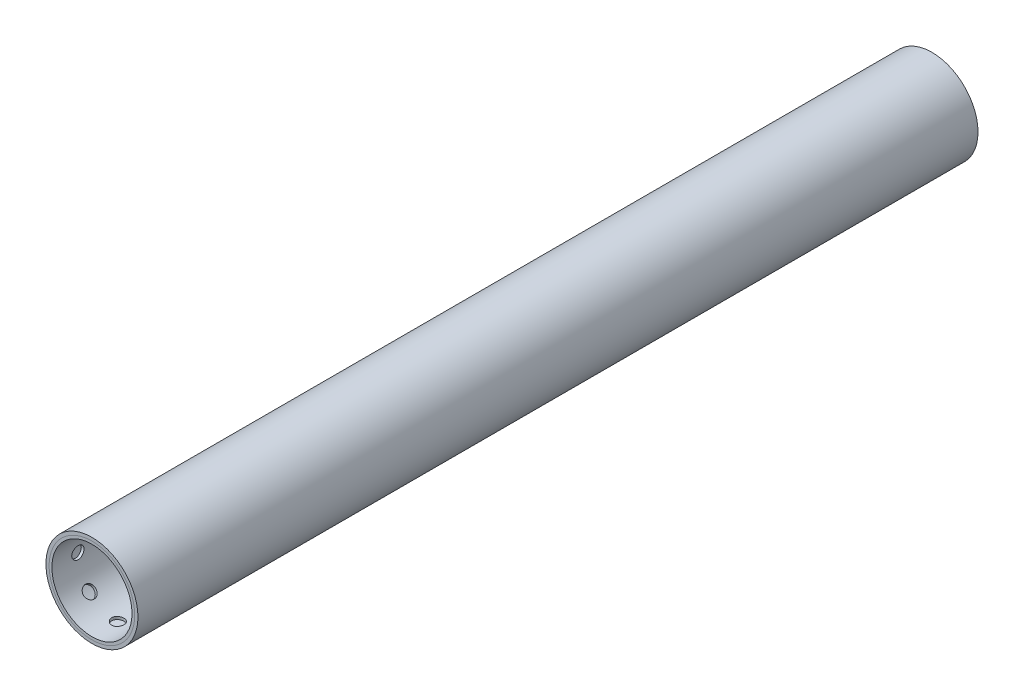
SolidWorks part; units mm, degrees
material "ASTM A53 Grade B"
ref_plane "Front Plane" through (0, 0, 0) normal (0, 0, 1) x (1, 0, 0)
ref_plane "Top Plane" through (0, 0, 0) normal (0, 1, 0) x (1, 0, 0)
ref_plane "Right Plane" through (0, 0, 0) normal (1, 0, 0) x (0, 0, -1)
sketch "Croquis1" plane through (0, 0, 0) normal (0, 0, 1) x (1, 0, 0)
  circle A0 centre (0, 0) radius 26.2509
  circle A1 centre (0, 0) radius 28.0509
  dimension "D1" = 52.5018
  dimension "D2" = 56.1018
extrude "Saliente-Extruir1" add sketch "Croquis1" against normal blind 550.5
sketch "Croquis2" plane through (0, 0, 0) normal (0, 0, 1) x (1, 0, 0)
  circle A0 centre (0, 0) radius 30.1625
  circle A3 centre (0, 0) radius 28.0509 construction
  circle A4 centre (0, 0) radius 28.0509
  dimension "D1" = 60.325
sketch "Croquis3" plane through (0, 0, 0) normal (1, 0, 0) x (0, 0, -1)
  line L0 (550.5, 28.0509) -> (535, 28.0509) construction
  point P4 (535, 28.0509)
  dimension "D1" = 15.5
sketch "Croquis14" plane through (0, 0, 0) normal (1, 0, 0) x (0, 0, -1)
  line L0 (550.5, 28.0509) -> (0, 28.0509) construction
  point P0 (17, 28.0509)
  dimension "D1" = 17
hole_wizard "Ø8.0mm Dowel Hole1" positions "Croquis3D7" profile "Croquis13" hole size "Ø8.0" standard "ANSI Metric"
sketch3d "Croquis3D7"
  point P0 (0, 28.0509, -535)
  point P4 (0, 0, 0)
  point P7 (0, 0, 0)
sketch "Croquis13" plane through (0, 28.0509, -535) normal (1, 0, 0) x (0, 0, 1)
  line L0 (0, 0) -> (0, 9.4034)
  line L1 (0, 9.4034) -> (4, 7)
  line L2 (4, 7) -> (4, 0)
  line L5 (4, 0) -> (0, 0)
  line L10 (0, 9.4034) -> (-4, 7) construction
  line L11 (0, -6.35) -> (0, 107.95) construction
  dimension "Hole Dia." = 8
  dimension "Hole Depth" = 7
  dimension "Drill Angle" = 118
hole_wizard "Ø8.0mm Dowel Hole2" positions "Croquis3D10" profile "Croquis17" hole size "Ø8.0" standard "ANSI Metric"
sketch3d "Croquis3D10"
  point P0 (0, 28.0509, -17)
  point P2 (0, 0, 0)
sketch "Croquis17" plane through (0, 28.0509, -17) normal (1, 0, 0) x (0, 0, 1)
  line L0 (0, 0) -> (0, 9.4034)
  line L1 (0, 9.4034) -> (4, 7)
  line L2 (4, 7) -> (4, 0)
  line L5 (4, 0) -> (0, 0)
  line L10 (0, 9.4034) -> (-4, 7) construction
  line L11 (0, -6.35) -> (0, 107.95) construction
  dimension "Hole Dia." = 8
  dimension "Hole Depth" = 7
  dimension "Drill Angle" = 118
pattern_circular "MatrizC1" count 8 over 360 about axis through (0, 0, -550.5) along (0, 0, 1) of "Ø8.0mm Dowel Hole1", "Ø8.0mm Dowel Hole2"
extrude "Saliente-Extruir2" add sketch "Croquis2" against normal blind 550.5 separate body
equation "\"IDcase\"= 52.5018"
equation "\"D1@Croquis1\"=\"IDcase\""
equation "\"ODcase\"= \"IDcase\" + 2 * \"CaseThickness\""
equation "\"D2@Croquis1\"=\"ODcase\""
equation "\"CaseLength\"= 525mm + 25 + 0.5"
equation "\"D1@Saliente-Extruir1\"=\"CaseLength\""
equation "\"CaseThickness\"= 1.8mm"
equation "\"D1@Croquis2\"=2.375in"
equation "\"NozzleScrewLoc\"=15.5"
equation "\"D1@Croquis3\"=\"NozzleScrewLoc\""
equation "\"HeadCaseScrewLoc\"=17"
equation "\"D1@Saliente-Extruir2\"=\"CaseLength\""
